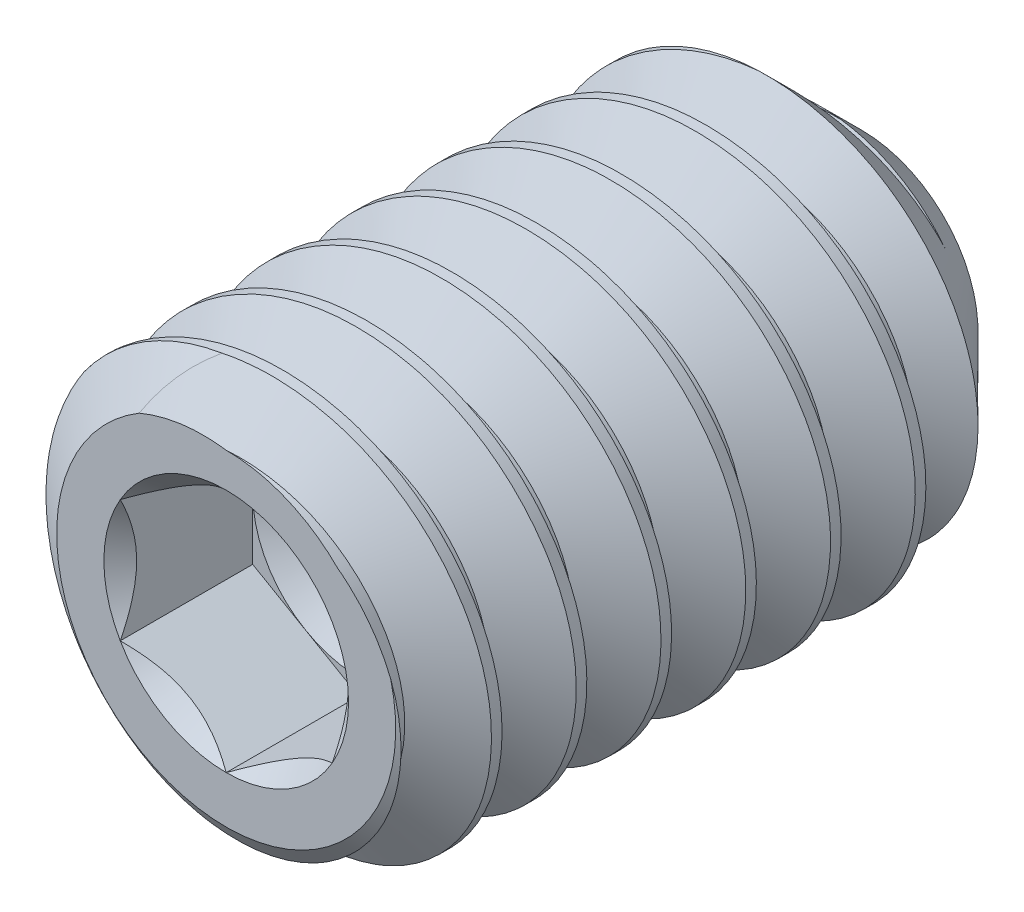
SolidWorks part; units mm, degrees
ref_plane "Front" through (0, 0, 0) normal (0, 0, 1) x (1, 0, 0)
ref_plane "Top" through (0, 0, 0) normal (0, 1, 0) x (1, 0, 0)
ref_plane "Right" through (0, 0, 0) normal (1, 0, 0) x (0, 0, -1)
sketch "Sketch22" plane through (0, 0, 0) normal (1, 0, 0) x (0, 0, -1)
  line L0 (-4.2398, 0) -> (-4.2398, 2.54)
  line L1 (-4.2398, 2.54) -> (-3.7952, 3.175)
  line L2 (-3.7952, 3.175) -> (3.85, 3.175)
  line L3 (3.85, 3.175) -> (5.2852, 1.7398)
  line L4 (5.2852, 1.7398) -> (4.2398, 0)
  line L5 (4.2398, 0) -> (-4.2398, 0)
  line L6 (4.2398, 0) -> (5.2852, 0) construction
  line L7 (5.2852, 0) -> (5.2852, 1.7398) construction
  line L8 (5.2852, -1.7398) -> (4.2398, 0) construction
  line L9 (-3.7952, -3.175) -> (3.85, -3.175) construction
  dimension "Dia" = 6.35
  dimension "Length" = 9.525
  dimension "D3" = 35
  dimension "D5" = 118
  dimension "D6" = 45
  dimension "D7" = 5.08
revolve "Revolve1" add sketch "Sketch22" angle 360 about L6
ref_plane "Plane1" through (0, 0, -5.2852) normal (0, 0, 1) x (1, 0, 0)
sketch "Sketch27" plane through (0, 0, -5.2852) normal (0, 0, 1) x (1, 0, 0)
  circle A0 centre (0, 0) radius 3.175 construction
  circle A1 centre (0, 0) radius 3.175
curve "Helix/Spiral1" pitch 1.27 height 10.795 radius 3.175 centre (0, 0, -5.2852) axis (0, 0, 1) start towards (0, 1, 0)
sketch "Sketch28" plane through (0, 0, 0) normal (1, 0, 0) x (0, 0, -1)
  line L0 (5.2852, 3.175) -> (6.3964, 3.175)
  line L1 (6.3964, 3.175) -> (5.9202, 2.3501)
  line L2 (5.9202, 2.3501) -> (5.7614, 2.3501)
  line L3 (5.7614, 2.3501) -> (5.2852, 3.175)
  line L4 (5.5233, 2.7626) -> (6.1583, 2.7626) construction
  line L6 (-3.7952, 3.175) -> (3.85, 3.175) construction
  line L7 (5.2852, 3.4925) -> (5.2852, -3.4925) construction
  dimension "D1" = 0.1588
  dimension "D3" = 60
  dimension "D2" = 0.635
sweep "Cut-Sweep2" cut profiles "Sketch28" path "Helix/Spiral1" align with end faces yes
sketch "Sketch23" plane through (0, 0, 4.2398) normal (0, 0, 1) x (1, 0, 0)
  line L1 (0, 1.8331) -> (-1.5875, 0.9165)
  line L2 (-1.5875, 0.9165) -> (-1.5875, -0.9165)
  line L3 (-1.5875, -0.9165) -> (0, -1.8331)
  line L4 (0, -1.8331) -> (1.5875, -0.9165)
  line L5 (1.5875, -0.9165) -> (1.5875, 0.9165)
  line L6 (1.5875, 0.9165) -> (0, 1.8331)
  circle A0 centre (0, 0) radius 1.5875 construction
  dimension "Hex" = 3.175
extrude "Cut-Extrude10" cut sketch "Sketch23" against normal blind 1.9844
sketch "Sketch24" plane through (0, 0, 4.2398) normal (0, 0, 1) x (1, 0, 0)
  circle A0 centre (0, 0) radius 1.8331
extrude "Cut-Extrude11" cut sketch "Sketch24" against normal through all draft 45
sketch "Sketch26" plane through (0, 0, 2.2554) normal (0, 0, 1) x (1, 0, 0)
  circle A0 centre (0, 0) radius 1.5875 construction
  circle A1 centre (0, 0) radius 1.5875
extrude "Cut-Extrude12" cut sketch "Sketch26" against normal through all draft 60
sketch "Sketch30" plane through (0, 0, 0) normal (1, 0, 0) x (0, 0, -1)
  line L0 (-3.7952, 3.175) -> (3.85, 3.175) construction
  line L1 (-4.2398, 0) -> (-4.2398, 2.54) construction
  line L2 (5.2852, 0) -> (5.2852, 1.7398) construction
  line L3 (-3.7952, -3.175) -> (3.85, -3.175) construction
  point P0 (-4.2398, 3.175)
  point P1 (5.2852, 3.175)
  point P2 (5.2852, -3.175)
  point P11 (0.8402, -3.175)
  dimension "D1" = 4.445
sketch "Sketch31" plane through (0, 0, 0) normal (1, 0, 0) x (0, 0, -1)
  line L2 (4.2398, 0) -> (5.2852, -1.7398)
  line L3 (5.2852, 1.7398) -> (4.2398, 0)
equation "\"D7@Sketch22\"=\"Dia@Sketch22\"*.8"
equation "\"D1@Sketch28\" = \"D4@Helix/Spiral1\" * .125"
equation "\"D3@Helix/Spiral1\" = \"Length@Sketch22\" + \"D4@Helix/Spiral1\""
equation "\"D1@Sketch30\" = \"D4@Helix/Spiral1\" * 3.5"
equation "\"hex Depth@Cut-Extrude10\" = \"Hex@Sketch23\" * .625"
equation "\"D2@Sketch28\" = \"D4@Helix/Spiral1\" * .5"
